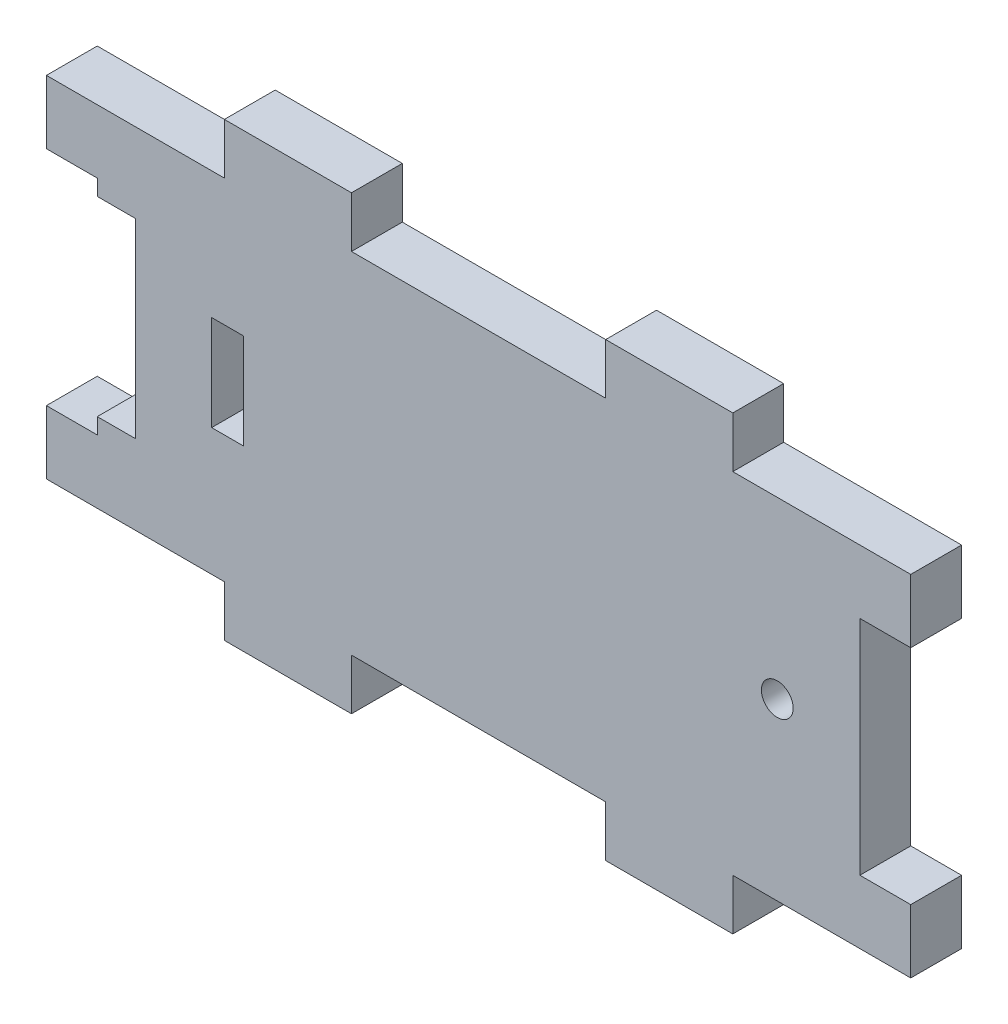
SolidWorks part; units mm, degrees
ref_plane "Front Plane" through (0, 0, 0) normal (0, 0, 1) x (1, 0, 0)
ref_plane "Top Plane" through (0, 0, 0) normal (0, 1, 0) x (1, 0, 0)
ref_plane "Right Plane" through (0, 0, 0) normal (1, 0, 0) x (0, 0, -1)
sketch "Sketch1" plane through (0, 0, 0) normal (0, 0, 1) x (1, 0, 0)
  line L1 (-60, 27.5) -> (60, 27.5)
  line L2 (-60, 27.5) -> (-60, -27.5)
  line L3 (-60, -27.5) -> (60, -27.5)
  line L4 (60, 27.5) -> (60, -27.5)
  line L5 (-42, -7.5) -> (-37, -7.5)
  line L6 (-42, -7.5) -> (-42, 7.5)
  line L7 (-42, 7.5) -> (-37, 7.5)
  line L8 (-37, -7.5) -> (-37, 7.5)
  circle A0 centre (47, 0) radius 2.5
  point P4 (0, 27.5)
  point P6 (60, 0)
  point P13 (0, 0)
  dimension "D6" = 13
  dimension "D1" = 55
  dimension "D2" = 120
  dimension "D3" = 15
  dimension "D4" = 20
  dimension "D5" = 18
extrude "Boss-Extrude1" add sketch "Sketch1" along normal blind 8
sketch "Sketch2" plane through (0, 0, 8) normal (0, 0, 1) x (1, 0, 0)
  line L0 (-60, 27.5) -> (-60, -27.5) construction
  line L1 (-92.7508, 15) -> (-54, 15)
  line L2 (-92.7508, 15) -> (-92.7508, -15)
  line L3 (-92.7508, -15) -> (-54, -15)
  line L4 (-54, 15) -> (-54, -15)
  point P4 (-54, 0)
  point P7 (-60, 0)
  dimension "D1" = 30
  dimension "D2" = 6
extrude "Cut-Extrude1" cut sketch "Sketch2" against normal up to next
sketch "Sketch4" plane through (60, 0, 0) normal (1, 0, 0) x (0, 0, -1)
  line L1 (-8, 27.5) -> (0, 27.5)
  line L2 (-8, 27.5) -> (-8, 17.5)
  line L3 (-8, 17.5) -> (0, 17.5)
  line L4 (0, 27.5) -> (0, 17.5)
  line L5 (-8, 27.5) -> (0, 27.5) construction
  line L6 (0, -27.5) -> (0, 27.5) construction
  line L7 (-23.1797, 0) -> (12.6777, 0) construction
  line L8 (-8, -27.5) -> (-8, -17.5)
  line L9 (-8, -27.5) -> (0, -27.5)
  line L10 (0, -27.5) -> (0, -17.5)
  line L11 (-8, -17.5) -> (0, -17.5)
  dimension "D1" = 10
extrude "Boss-Extrude3" add sketch "Sketch4" along normal blind 8
sketch "Sketch6" plane through (0, -27.5, 0) normal (0, -1, 0) x (1, 0, 0)
  line L0 (0, 25.2996) -> (0, -15.5638) construction
  line L1 (-40, 8) -> (-20, 8)
  line L2 (-40, 8) -> (-40, 0)
  line L3 (-40, 0) -> (-20, 0)
  line L4 (-20, 8) -> (-20, 0)
  line L5 (20, 8) -> (20, 0)
  line L6 (40, 0) -> (20, 0)
  line L7 (40, 8) -> (40, 0)
  line L8 (40, 8) -> (20, 8)
  line L9 (-60, 8) -> (68, 8) construction
  line L10 (-60, 0) -> (68, 0) construction
  dimension "D1" = 20
  dimension "D2" = 40
extrude "Boss-Extrude4" add sketch "Sketch6" along normal blind 8
ref_plane "Plane1" through (0, 0, 0) normal (0, -1, 0) x (-1, 0, 0)
mirror "Mirror2" about plane through (0, 0, 0) normal (0, -1, 0) of "Boss-Extrude4"
ref_plane "Plane2" through (0, 0, 0) normal (-1, 0, 0) x (0, 0, 1)
mirror "Mirror3" about plane through (0, 0, 0) normal (-1, 0, 0) of "Boss-Extrude3"
